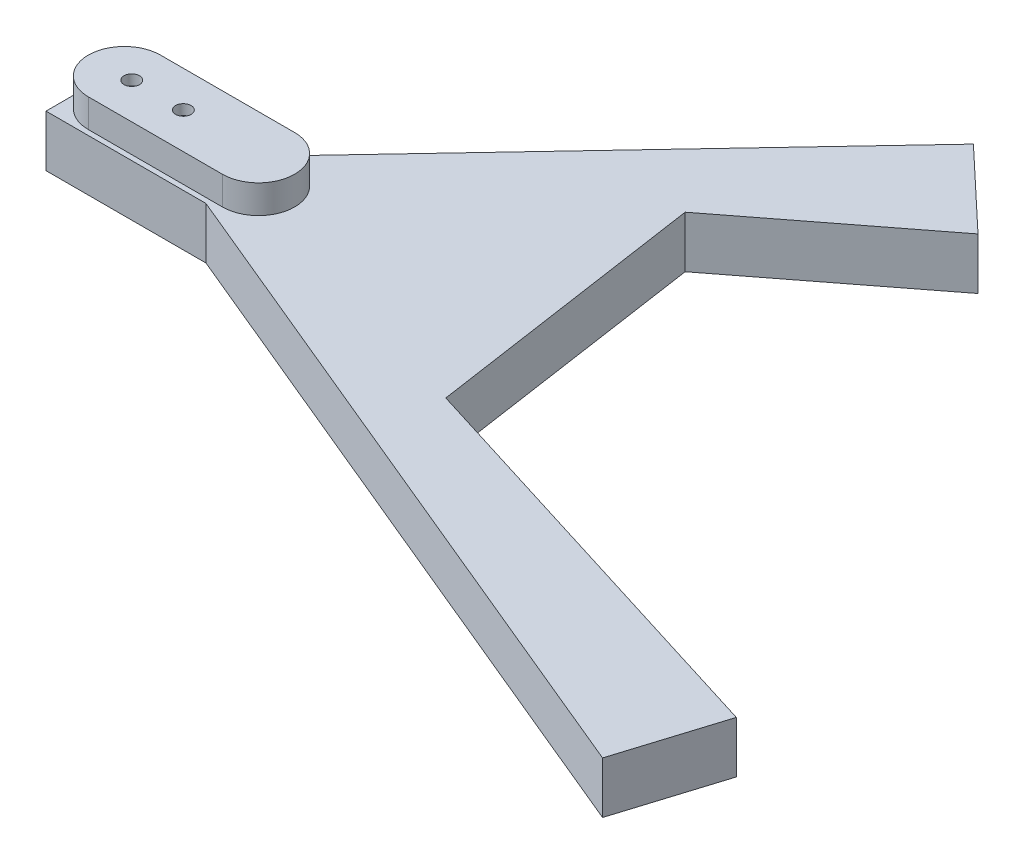
SolidWorks part; units mm, degrees
ref_plane "Front Plane" through (0, 0, 0) normal (0, 0, 1) x (1, 0, 0)
ref_plane "Top Plane" through (0, 0, 0) normal (0, 1, 0) x (1, 0, 0)
ref_plane "Right Plane" through (0, 0, 0) normal (1, 0, 0) x (0, 0, -1)
sketch "Sketch1" plane through (0, 0, 0) normal (0, 1, 0) x (1, 0, 0)
  line L0 (20.1887, 4.5283) -> (84.5984, 72.8611)
  line L1 (-10.8113, 4.5283) -> (20.1887, 4.5283)
  line L2 (-10.8113, 4.5283) -> (-10.8113, -11.4717)
  line L3 (-10.8113, -11.4717) -> (20.1887, -11.4717)
  line L4 (20.1887, 4.5283) -> (20.1887, -11.4717)
  line L5 (84.5984, 72.8611) -> (100.1264, 58.2245)
  line L6 (100.1264, 58.2245) -> (20.1887, -3.4717)
  line L7 (20.1887, -3.4717) -> (157.8481, -46.3414)
  line L8 (157.8481, -46.3414) -> (151.6929, -66.1064)
  line L9 (151.6929, -66.1064) -> (20.1887, -11.4717)
  line L10 (68.0937, 33.5015) -> (76.0843, -20.8786)
  dimension "D1" = 31
  dimension "D2" = 16
extrude "Boss-Extrude1" add sketch "Sketch1" along normal blind 10 contours L6 L5 L0 L4 | L9 L8 L7 L4 | L4 L1 L2 L3 | L10 L6 L7 region at (4.6887, 0, 3.4717) region at (63.1102, 0, -39.0489) region at (97.9512, 0, 35.6107) region at (54.7889, 0, -3.0504)
sketch "Sketch2" plane through (0, 10, 0) normal (0, 1, 0) x (1, 0, 0)
  line L0 (-3.6164, -3.4717) -> (22.3836, -3.4717) construction
  line L1 (-3.6164, 3.5283) -> (22.3836, 3.5283)
  line L2 (-3.6164, -10.4717) -> (22.3836, -10.4717)
  line L9 (-10.8113, -11.4717) -> (20.1887, -11.4717) construction
  arc A0 (-3.6164, 3.5283) -> (-3.6164, -10.4717) centre (-3.6164, -3.4717) ccw
  arc A1 (22.3836, -10.4717) -> (22.3836, 3.5283) centre (22.3836, -3.4717) ccw
  point P2 (9.3836, -3.4717)
  dimension "D1" = 26
  dimension "D2" = 14
  dimension "D3" = 1
extrude "Boss-Extrude2" add sketch "Sketch2" along normal blind 5.5
sketch "Sketch3" plane through (0, 15.5, 0) normal (0, 1, 0) x (1, 0, 0)
  line L1 (22.3836, 3.5283) -> (-3.6164, 3.5283) construction
  circle A0 centre (-2.1895, -3.4717) radius 1.5
  circle A1 centre (7.8105, -3.4717) radius 1.5
  dimension "D1" = 7
  dimension "D3" = 7
  dimension "D2" = 10
extrude "Cut-Extrude1" cut sketch "Sketch3" against normal blind 20
sketch "Sketch4" plane through (0, 0, 0) normal (0, -1, 0) x (1, 0, 0)
  line L0 (-2.1895, 3.4717) -> (7.8105, 3.4717) construction
  line L1 (-2.1895, 7.9717) -> (7.8105, 7.9717)
  line L2 (-2.1895, -1.0283) -> (7.8105, -1.0283)
  arc A0 (-2.1895, 7.9717) -> (-2.1895, -1.0283) centre (-2.1895, 3.4717) ccw
  arc A1 (7.8105, -1.0283) -> (7.8105, 7.9717) centre (7.8105, 3.4717) ccw
  point P4 (2.8105, 3.4717)
  dimension "D1" = 9
extrude "Cut-Extrude2" cut sketch "Sketch4" against normal blind 13.5
